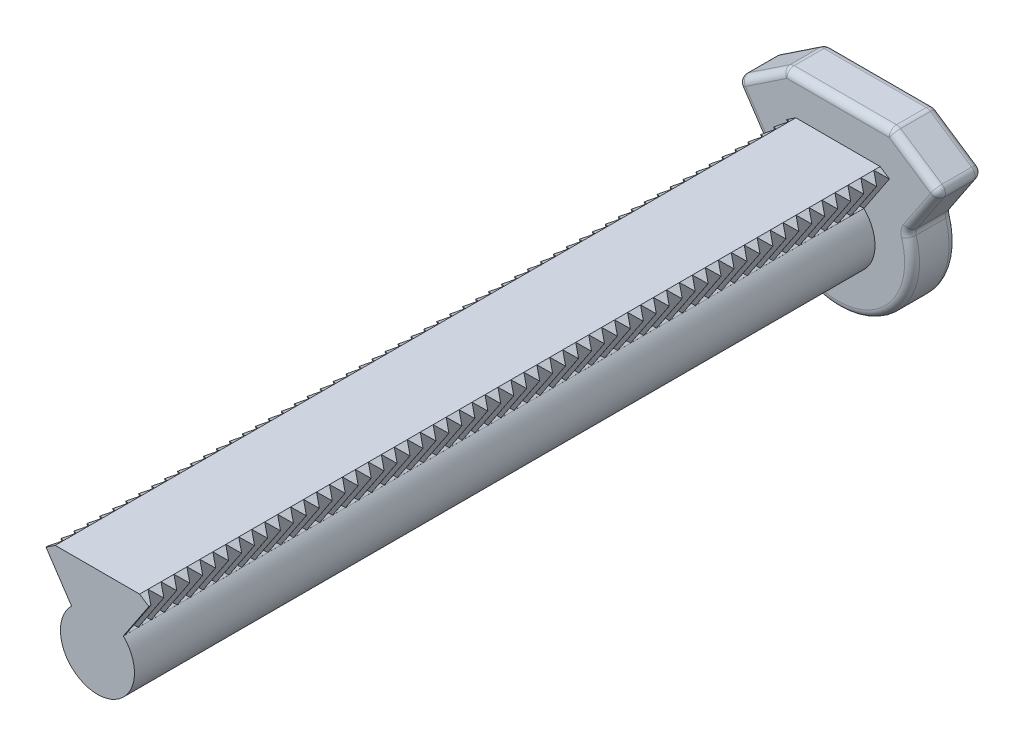
SolidWorks part; units mm, degrees
ref_plane "Alzado" through (0, 0, 0) normal (0, 0, 1) x (1, 0, 0)
ref_plane "Planta" through (0, 0, 0) normal (0, 1, 0) x (1, 0, 0)
ref_plane "Vista lateral" through (0, 0, 0) normal (1, 0, 0) x (0, 0, -1)
sketch "Croquis1" plane through (0, 0, 0) normal (0, 0, 1) x (1, 0, 0)
  line L0 (-3.4937, 3.5769) -> (3.4937, 3.5769)
  line L1 (3.4937, 3.5769) -> (7.5, 9.5769)
  line L2 (7.5, 9.5769) -> (-7.5, 9.5769)
  line L3 (-7.5, 9.5769) -> (-3.4937, 3.5769)
  circle A0 centre (0, 0) radius 5
  dimension "D1" = 10
  dimension "D2" = 15
  dimension "D3" = 6
extrude "Saliente-Extruir1" add sketch "Croquis1" along normal blind 100 contours L0 A0 | L0 A0 | A0 L1 L2 L3 region at (0, 4.1537, 0) region at (0, 7.264, 0) region at (0, -0.3965, 0)
ref_plane "Plano3" through (0, 0, 0) normal (1, 0, 0) x (0, 0, -1)
chamfer "Chaflán2" distance 1 angle 90 2 edges at (-7.5, 9.5769, 50) (7.5, 9.5769, 50) first distance on face at (-5.4969, 6.5769, 50) first distance on face at (5.4969, 6.5769, 50)
sketch "Croquis2" plane through (6.1802, 9.2557, 0) normal (0.5553, 0.8316, 0) x (0.8316, -0.5553, 0)
  line L5 (0.9193, 0) -> (0.9193, -1.7293)
  line L6 (0.9193, 0) -> (0.9193, -100) construction
  line L7 (0.9193, -1.7293) -> (-0.5783, -0.8647)
  line L8 (-0.5783, -100) -> (-0.5783, 0) construction
  line L9 (-0.5783, -0.8647) -> (0.9193, 0)
extrude "Cortar-Extruir1" cut sketch "Croquis2" against normal blind 6.2
pattern_linear "MatrizL1" count 57 spacing 1.75 along (0, 0, 1) of "Cortar-Extruir1"
mirror "Simetría1" about plane through (0, 0, 0) normal (1, 0, 0) of "MatrizL1"
sketch "Croquis3" plane through (0, 0, 0) normal (0, 0, -1) x (-1, 0, 0)
  line L14 (9.3985, 3.416) -> (13.8795, 10.1269)
  line L15 (13.8795, 10.1269) -> (7.215, 14.5769)
  line L16 (7.215, 14.5769) -> (-7.215, 14.5769)
  line L17 (-7.215, 14.5769) -> (-13.8795, 10.1269)
  line L18 (-13.8795, 10.1269) -> (-9.3985, 3.416)
  line L19 (9.3985, 3.416) -> (13.8795, 10.1269)
  line L20 (13.8795, 10.1269) -> (7.215, 14.5769)
  line L21 (7.215, 14.5769) -> (-7.215, 14.5769)
  line L22 (-7.215, 14.5769) -> (-13.8795, 10.1269)
  line L23 (-13.8795, 10.1269) -> (-9.3985, 3.416)
  arc A2 (-9.3985, 3.416) -> (9.3985, 3.416) centre (0, 0) ccw
  arc A3 (-9.3985, 3.416) -> (9.3985, 3.416) centre (0, 0) ccw
  dimension "D1" = 5
extrude "Saliente-Extruir2" add sketch "Croquis3" along normal blind 6
fillet "Redondeo1" radius 1 18 edges at (0, -10, 0) (-9.3985, 3.416, -3) (-11.639, 6.7715, 0) (9.3985, 3.416, -3) (11.639, 6.7715, 0) (13.8795, 10.1269, -3) (10.5472, 12.3519, 0) (-13.8795, 10.1269, -3) (-10.5472, 12.3519, 0) (-7.215, 14.5769, -3) (7.215, 14.5769, -3) (0, 14.5769, 0) (11.639, 6.7715, -6) (10.5472, 12.3519, -6) (0, 14.5769, -6) (-10.5472, 12.3519, -6) (-11.639, 6.7715, -6) (0, -10, -6)
